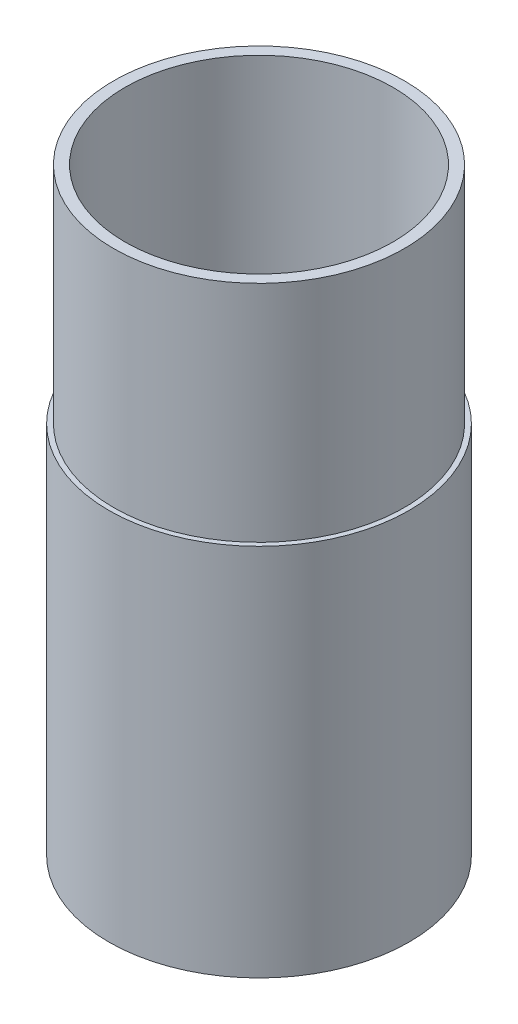
SolidWorks part; units mm, degrees
material "E-Glass Fiber"
ref_plane "Front Plane" through (0, 0, 0) normal (0, 0, 1) x (1, 0, 0)
ref_plane "Top Plane" through (0, 0, 0) normal (0, 1, 0) x (1, 0, 0)
ref_plane "Right Plane" through (0, 0, 0) normal (1, 0, 0) x (0, 0, -1)
sketch "Sketch1" plane through (0, 0, 0) normal (0, 0, 1) x (1, 0, 0)
  line L0 (0, 0) -> (0, 49.7577) construction
  line L1 (22.7624, -43.5737) -> (24.6928, -43.5737)
  line L2 (22.7624, -43.5737) -> (22.7624, 58.0263)
  line L3 (22.7624, 58.0263) -> (24.6928, 58.0263)
  line L4 (24.6928, -43.5737) -> (24.6928, 58.0263)
  line L5 (24.6928, -43.5737) -> (25.5143, -43.5737)
  line L6 (24.6928, -43.5737) -> (24.6928, 19.9263)
  line L7 (24.6928, 19.9263) -> (25.5143, 19.9263)
  line L8 (25.5143, -43.5737) -> (25.5143, 19.9263)
  line L9 (25.5143, -729.3737) -> (25.5143, 19.9263) construction
  point P10 (22.3799, 77.2018)
  point P12 (24.3103, 77.2018)
  point P14 (22.3799, -24.3982)
  point P16 (25.5143, -24.3982)
  point P18 (25.5143, 19.9263)
  point P21 (25.5143, 19.9263)
revolve "Revolve1" add sketch "Sketch1" angle 360 about L0 region at (23.7276, 7.2263, 0) region at (25.1035, -11.8237, 0)
